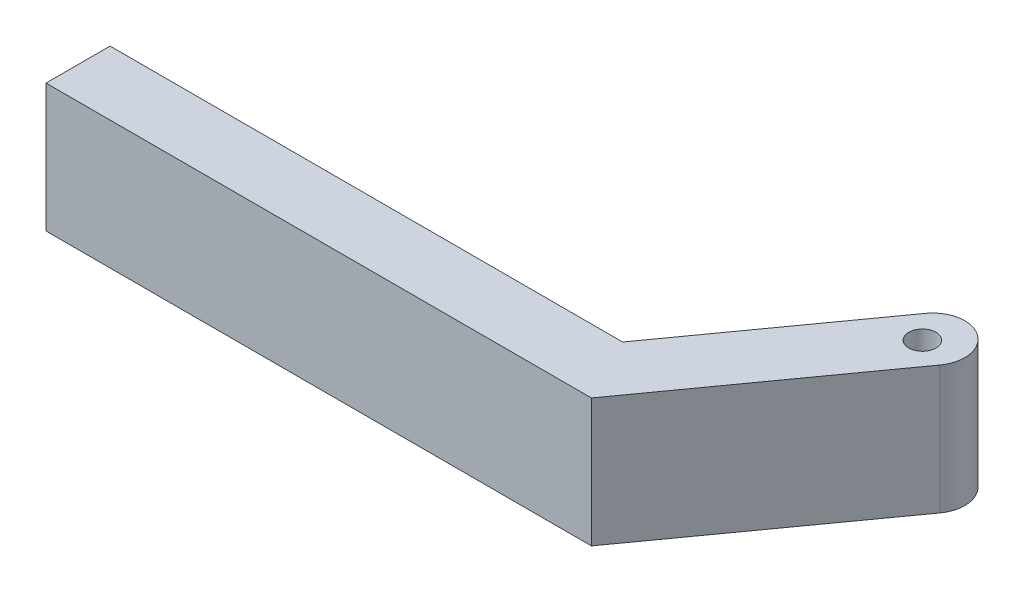
SolidWorks part; units mm, degrees
ref_plane "Front Plane" through (0, 0, 0) normal (0, 0, 1) x (1, 0, 0)
ref_plane "Top Plane" through (0, 0, 0) normal (0, 1, 0) x (1, 0, 0)
ref_plane "Right Plane" through (0, 0, 0) normal (1, 0, 0) x (0, 0, -1)
sketch "Sketch2" plane through (0, 0, 0) normal (0, 1, 0) x (1, 0, 0)
  line L5 (-12.5392, -37.888) -> (0.0062, -20.4255)
  line L7 (-63.3392, -44.238) -> (-12.5392, -44.238)
  line L8 (-63.3392, -44.238) -> (-63.3392, -37.888)
  line L9 (-63.3392, -37.888) -> (-12.5392, -37.888)
  line L10 (-12.5392, -44.238) -> (-12.5392, -37.888) construction
  line L11 (-63.3392, -44.238) -> (-12.5392, -37.888) construction
  line L12 (-63.3392, -37.888) -> (-12.5392, -44.238) construction
  line L14 (-12.5392, -44.238) -> (-9.2823, -44.238)
  line L18 (5.1633, -24.1305) -> (-9.2823, -44.238)
  line L19 (0.0062, -20.4255) -> (5.1633, -24.1305) construction
  arc A2 (0.0062, -20.4255) -> (5.1633, -24.1305) centre (2.5848, -22.278) cw
  point P4 (0, 0)
  point P5 (-37.9392, -41.063)
  dimension "D2" = 6.35
  dimension "D3" = 17.4625
  dimension "D4" = 6.35
  dimension "D10" = 50.8
extrude "Boss-Extrude1" add sketch "Sketch2" along normal blind 12.7
hole_wizard "#6-32 Tapped Hole1" positions "Sketch3" profile "Sketch4" tap size "#6-32" standard "ANSI Inch" end condition through all
sketch "Sketch3" plane through (0, 12.7, 0) normal (0, 1, 0) x (1, 0, 0)
  line L0 (-9.2823, -44.238) -> (5.1633, -24.1305) construction
  arc A0 (5.1633, -24.1305) -> (0.0062, -20.4255) centre (2.5848, -22.278) ccw construction
  point P0 (2.1563, -22.8744)
  point P6 (4.4373, -19.6994)
  dimension "D1" = 3.175
  dimension "D2" = 3.175
cosmetic thread "Hole Thread1"
sketch "Sketch4" plane through (2.1563, 12.7, 22.8744) normal (1, 0, 0) x (0, 0, 1)
  line L0 (0, 0) -> (0, 12.7)
  line L1 (0, 12.7) -> (1.3525, 12.7)
  line L2 (1.3525, 12.7) -> (1.3525, 0)
  line L5 (1.3525, 0) -> (0, 0)
  line L11 (0, -6.35) -> (0, 107.95) construction
  dimension "Thru Tap Drill Dia." = 2.7051
  dimension "Thru Tap Drill Depth" = 12.7
